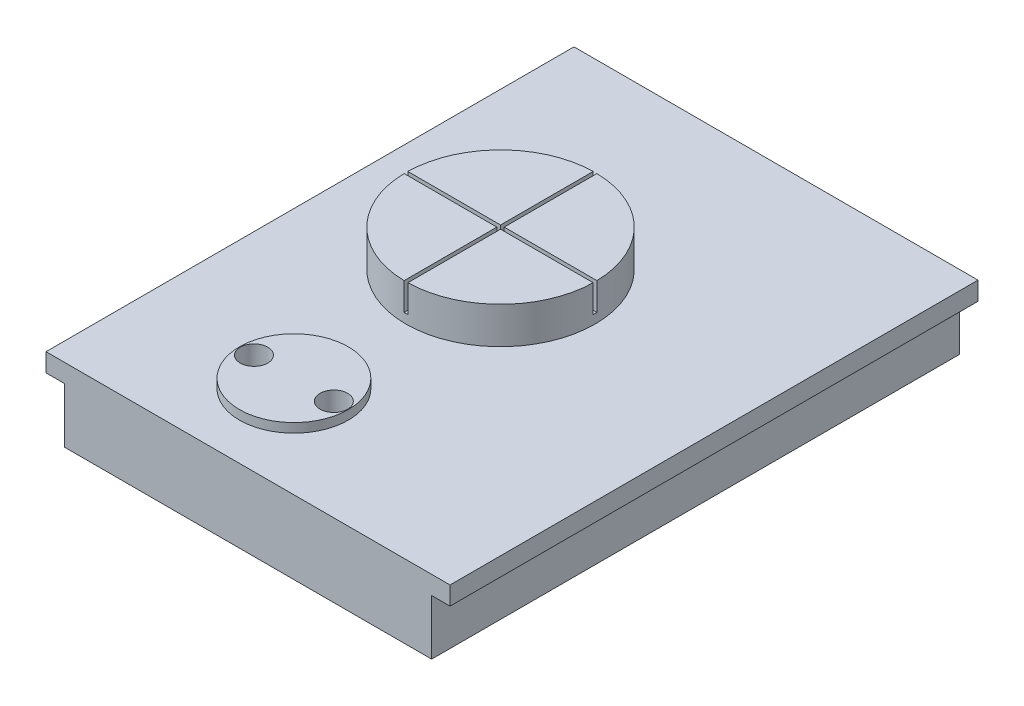
SolidWorks part; units mm, degrees
ref_plane "Front Plane" through (0, 0, 0) normal (0, 0, 1) x (1, 0, 0)
ref_plane "Top Plane" through (0, 0, 0) normal (0, 1, 0) x (1, 0, 0)
ref_plane "Right Plane" through (0, 0, 0) normal (1, 0, 0) x (0, 0, -1)
sketch "Sketch1" plane through (0, 0, 0) normal (0, 1, 0) x (1, 0, 0)
  line L1 (-15, -10) -> (25, -10)
  line L2 (-15, -10) -> (-15, 47.5)
  line L3 (-15, 47.5) -> (25, 47.5)
  line L4 (25, -10) -> (25, 47.5)
  line L5 (-17, 47.5) -> (-15, 47.5)
  line L6 (-17, 47.5) -> (-17, -10)
  line L7 (-17, -10) -> (-15, -10)
  line L8 (-15, 47.5) -> (-15, -10)
  line L9 (25, -10) -> (27, -10)
  line L10 (25, -10) -> (25, 47.5)
  line L11 (25, 47.5) -> (27, 47.5)
  line L12 (27, -10) -> (27, 47.5)
  circle A0 centre (0, 0) radius 4.35 construction
  circle A1 centre (-4.35, 0) radius 1.5
  circle A2 centre (4.35, 0) radius 1.5
  circle A3 centre (0, 0) radius 5.85 construction
  circle A4 centre (0, 0) radius 5.925
  circle A5 centre (0, 22.5) radius 10.3
  point P23 (0, 0)
  point P24 (29.1064, -8.1296)
  point P25 (0, 0)
  point P26 (0, 0)
  point P27 (-40.929, 45.384)
  dimension "D1" = 11.85
  dimension "D2" = 11.7
  dimension "D3" = 3
  dimension "D5" = 20.6
  dimension "D4" = 22.5
  dimension "D6" = 2
  dimension "D7" = 15
  dimension "D8" = 10
  dimension "D9" = 25
  dimension "D10" = 25
extrude "Boss-Extrude1" add sketch "Sketch1" against normal blind 8 contours A5 | L1 L4 L3 L2 A5 A4 | A4 A1 A2 region at (-14.2996, 0, -18.75) region at (0, 0, 0) region at (0, 0, -22.5)
extrude "Boss-Extrude2" add sketch "Sketch1<3>" against normal blind 2 contours L6 L7 L2 L5 | L9 L12 L11 L4 region at (-16, 0, -18.75) region at (26, 0, -18.75)
sketch "Sketch1<3>" plane through (0, 0, 0) normal (0, 1, 0) x (1, 0, 0) same geometry as "Sketch1"
extrude "Boss-Extrude3" add sketch "Sketch1<4>" along normal blind 4 contours A5 region at (0, 0, -22.5)
sketch "Sketch1<4>" plane through (0, 0, 0) normal (0, 1, 0) x (1, 0, 0) same geometry as "Sketch1"
extrude "Boss-Extrude4" add sketch "Sketch1<5>" along normal blind 1 contours A4 A1 A2 region at (0, 0, 0)
sketch "Sketch1<5>" plane through (0, 0, 0) normal (0, 1, 0) x (1, 0, 0) same geometry as "Sketch1"
sketch "Sketch2" plane through (0, -8, 0) normal (0, -1, 0) x (1, 0, 0)
  circle A0 centre (-4.35, 0) radius 1.9
  circle A1 centre (4.35, 0) radius 1.9
  circle M7 centre (-4.35, 0) radius 1.5
  circle M8 centre (4.35, 0) radius 1.5
  dimension "D1" = 3.8
extrude "Cut-Extrude1" cut sketch "Sketch2" against normal blind 6 contours A0 M7 | A1 M8 region at (-6.1963, -8, 0) region at (2.5037, -8, 0)
sketch "Sketch3" plane through (0, 4, 0) normal (0, 1, 0) x (1, 0, 0)
  line L0 (0, 12.2) -> (0, 32.8)
  line L1 (-10.3, 22.5) -> (10.3, 22.5)
  circle A0 centre (0, 22.5) radius 10.3 construction
  circle A1 centre (0, 22.5) radius 10.3 construction
extrude "Cut-Extrude-Thin1" cut sketch "Sketch3" against normal blind 3 thin thin type two direction wall 0.2 second wall 0.2
